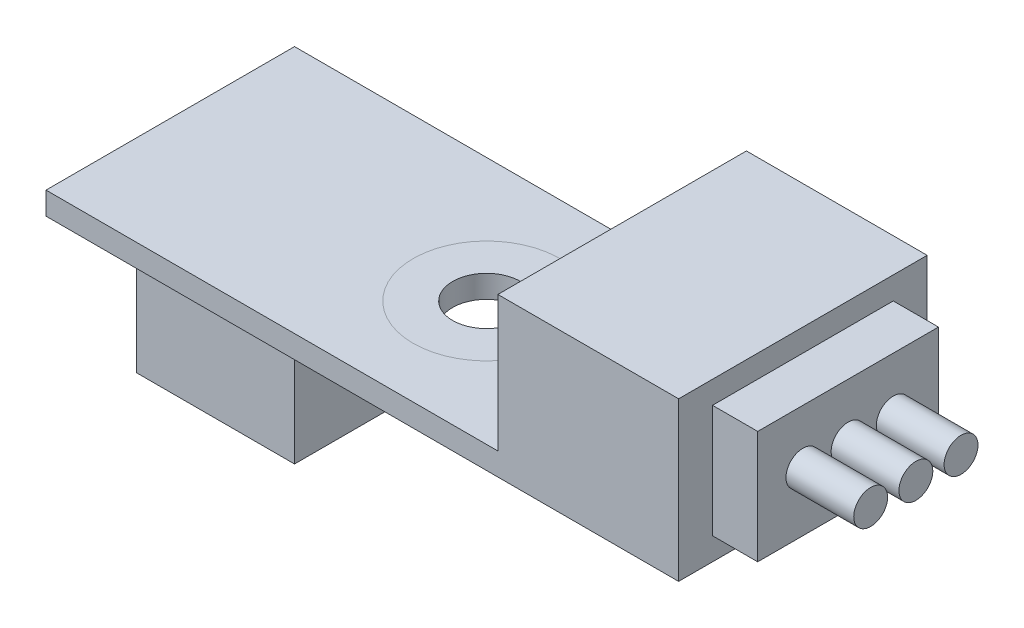
SolidWorks part; units mm, degrees
ref_plane "Front Plane" through (0, 0, 0) normal (0, 0, 1) x (1, 0, 0)
ref_plane "Top Plane" through (0, 0, 0) normal (0, 1, 0) x (1, 0, 0)
ref_plane "Right Plane" through (0, 0, 0) normal (1, 0, 0) x (0, 0, -1)
sketch "Sketch1" plane through (0, 0, 0) normal (0, 1, 0) x (1, 0, 0)
  line L0 (-14, 0) -> (14, 0) construction
  line L1 (-14, -5.5) -> (14, -5.5)
  line L2 (-14, -5.5) -> (-14, 5.5)
  line L3 (-14, 5.5) -> (14, 5.5)
  line L4 (14, -5.5) -> (14, 5.5)
  line L5 (-14, -5.5) -> (14, 5.5) construction
  line L6 (-14, 5.5) -> (14, -5.5) construction
  line L7 (-6, -2.5) -> (-13, -2.5)
  line L8 (-6, -2.5) -> (-6, 2.5)
  line L9 (-6, 2.5) -> (-13, 2.5)
  line L10 (-13, -2.5) -> (-13, 2.5)
  line L11 (-6, -2.5) -> (-13, 2.5) construction
  line L12 (-6, 2.5) -> (-13, -2.5) construction
  line L13 (6, 5.5) -> (6, -5.5)
  circle A0 centre (0, 0) radius 1.5
  circle A1 centre (0, 0) radius 3.25
  point P0 (0, 0)
  point P9 (-9.5, 0)
  dimension "D3" = 3
  dimension "D4" = 6.5
  dimension "D1" = 11
  dimension "D2" = 28
  dimension "D5" = 7
  dimension "D6" = 5
  dimension "D7" = 1
  dimension "D8" = 8
extrude "Boss-Extrude1" add sketch "Sketch1" along normal blind 1 contours L13 L3 L2 L1 A1 L7 L10 L9 L8 | L10 L7 L8 L9 | A1 A0 | L3 L13 L1 L4 region at (-3.6063, 0, 0) region at (10, 0, 0) region at (-9.5, 0, 0) region at (-3.1581, 0, 0)
sketch "Sketch2" plane through (0, 0, 0) normal (0, 1, 0) x (1, 0, 0)
  circle A0 centre (0, 0) radius 3.25 construction
  circle A1 centre (0, 0) radius 3.25
split line "Split Line1"
extrude "Boss-Extrude2" add sketch "Sketch1<3>" against normal blind 7 contours L9 L10 L7 L8
sketch "Sketch1<3>" plane through (0, 0, 0) normal (0, 1, 0) x (1, 0, 0) same geometry as "Sketch1"
extrude "Boss-Extrude3" add sketch "Sketch1<4>" along normal blind 6 from surface contours L3 L13 L1 L4 region at (10, 0, 0) starting at face at (0, 1, 0)
sketch "Sketch1<4>" plane through (0, 0, 0) normal (0, 1, 0) x (1, 0, 0) same geometry as "Sketch1"
sketch "Sketch3" plane through (14, 0, 0) normal (1, 0, 0) x (0, 0, -1)
  line L1 (4, 6) -> (-4, 6)
  line L2 (4, 6) -> (4, 1)
  line L3 (4, 1) -> (-4, 1)
  line L4 (-4, 6) -> (-4, 1)
  line L5 (4, 6) -> (-4, 1) construction
  line L6 (4, 1) -> (-4, 6) construction
  line L7 (-5.5, 1) -> (5.5, 1) construction
  point P0 (0, 3.5)
  point P7 (0, 0)
  dimension "D1" = 5
  dimension "D2" = 8
extrude "Boss-Extrude4" add sketch "Sketch3" along normal blind 2
sketch "Sketch4" plane through (16, 0, 0) normal (1, 0, 0) x (0, 0, -1)
  line L0 (-2, 3.6038) -> (2, 3.6038) construction
  line L1 (0, 3.6038) -> (0, 0) construction
  circle A0 centre (-2, 3.6038) radius 0.75
  circle A1 centre (0, 3.6038) radius 0.75
  circle A2 centre (2, 3.6038) radius 0.75
  point P7 (0, 3.6038)
  dimension "D2" = 1.5
  dimension "D1" = 4
extrude "Boss-Extrude6" add sketch "Sketch4" along normal blind 3
